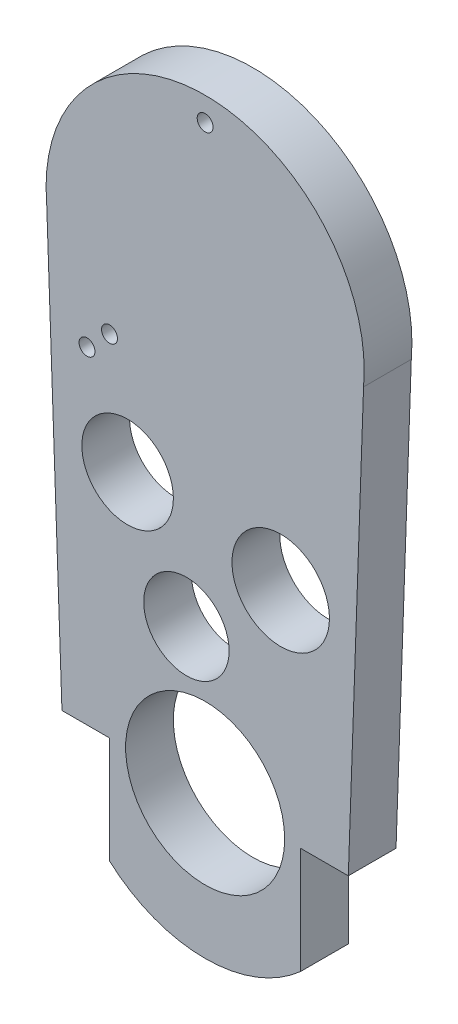
SolidWorks part; units mm, degrees
ref_plane "Plan de face" through (0, 0, 0) normal (0, 0, 1) x (1, 0, 0)
ref_plane "Plan de dessus" through (0, 0, 0) normal (0, 1, 0) x (1, 0, 0)
ref_plane "Plan de droite" through (0, 0, 0) normal (1, 0, 0) x (0, 0, -1)
sketch "Esquisse1" plane through (0, 0, 0) normal (0, 0, 1) x (1, 0, 0)
  line L0 (8.3168, 9) -> (0, 9) construction
  line L1 (0, 9) -> (0, 6) construction
  line L2 (0, 6) -> (8.0445, 6) construction
  line L3 (0, 0) -> (0, 28) construction
  line L4 (-7.5, 0) -> (-9.9591, 27.0962) construction
  line L5 (9.9591, 27.0962) -> (7.5, 0) construction
  line L6 (9.9591, 27.0962) -> (8.3168, 9) construction
  line L7 (8.0445, 6) -> (7.5, 0) construction
  line L8 (0, 0) -> (18.0723, 0) construction
  line L9 (7.5, 0) -> (6.6832, -9) construction
  line L12 (6.6832, -9) -> (0, -9) construction
  line L13 (0, -9) -> (0, -6) construction
  line L14 (0, -6) -> (-6.9555, -6) construction
  line L15 (-6.9555, -6) -> (-7.5, 0) construction
  line L16 (6, -6.7082) -> (6, 0)
  line L17 (6, 0) -> (9, 0)
  line L18 (9, 0) -> (9.9591, 27.0962)
  line L20 (-9, 0) -> (-9.9591, 27.0962)
  line L22 (-6, -6.7082) -> (-6, 0)
  line L23 (-6, 0) -> (-9, 0)
  line L24 (-7.4246, 20.5754) -> (0, 28) construction
  circle A0 centre (0, 0) radius 5
  circle A1 centre (0, 28) radius 10 construction
  arc A2 (-9.9591, 27.0962) -> (9.9591, 27.0962) centre (0, 28) cw
  arc A4 (9, 0) -> (-9, 0) centre (0, 0) cw construction
  arc A5 (-6, -6.7082) -> (6, -6.7082) centre (0, 0) ccw
  circle A6 centre (-4.8742, 15.0481) radius 2.8775
  circle A7 centre (4.7507, 13.4162) radius 3.0635
  circle A8 centre (-1.1774, 8.4871) radius 2.6843
  circle A9 centre (-7.4246, 20.5754) radius 0.5
  circle A10 centre (-6.0104, 21.9896) radius 0.5
  circle A11 centre (0, 28) radius 9 construction
  circle A12 centre (0, 36.5) radius 0.5
  point P35 (0, 0)
  dimension "D1" = 10
  dimension "D4" = 10
  dimension "D13" = 1
  dimension "D14" = 1
  dimension "D2" = 3
  dimension "D3" = 9
  dimension "D7" = 28
  dimension "D5" = 15
  dimension "D6" = 15
  dimension "D8" = 9
  dimension "D9" = 3
  dimension "D10" = 3
  dimension "D12" = 6
  dimension "D11" = 1
  dimension "D15" = 45
extrude "Boss.-Extru.1" add sketch "Esquisse1" along normal blind 3
equation "\"D8@Esquisse1\"=\"D3@Esquisse1\""
equation "\"D9@Esquisse1\"=\"D2@Esquisse1\""
